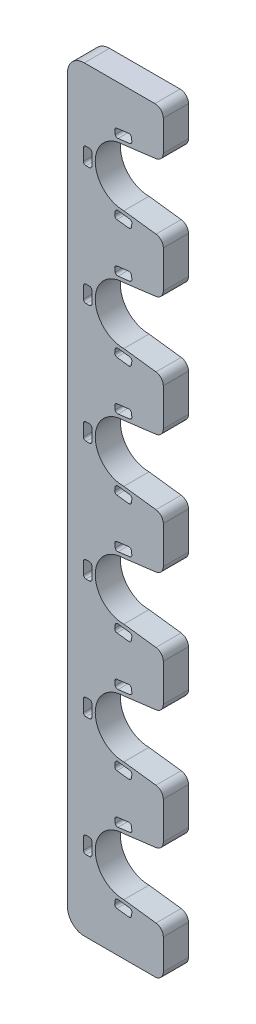
SolidWorks part; units mm, degrees
ref_plane "Front" through (0, 0, 0) normal (0, 0, 1) x (1, 0, 0)
ref_plane "Top" through (0, 0, 0) normal (0, 1, 0) x (1, 0, 0)
ref_plane "Right" through (0, 0, 0) normal (1, 0, 0) x (0, 0, -1)
sketch "Esquisse1" plane through (0, 0, 0) normal (0, 0, 1) x (1, 0, 0)
  line L1 (0, 0) -> (47, 0)
  line L2 (0, 0) -> (0, 450)
  line L3 (0, 450) -> (47, 450)
  line L4 (47, 0) -> (47, 450)
  dimension "D1" = 47
  dimension "D2" = 450
extrude "Boss.-Extru.1" add sketch "Esquisse1" along normal blind 15
sketch "Esquisse2" plane through (0, 0, 15) normal (0, 0, 1) x (1, 0, 0)
  line L0 (23.5, 0) -> (23.5, 450) construction
  line L1 (0, 0) -> (47, 0) construction
  line L2 (47, 450) -> (0, 450) construction
  line L3 (23.5, 225) -> (0, 225) construction
  line L4 (23.5, 154) -> (0, 154) construction
  line L5 (0, 450) -> (0, 0) construction
  line L6 (23.5, 83) -> (0, 83) construction
  line L7 (23.5, 367) -> (0, 367) construction
  line L8 (23.5, 296) -> (0, 296) construction
  circle A0 centre (23.5, 260.5) radius 17
  circle A1 centre (23.5, 189.5) radius 17
  circle A2 centre (23.5, 118.5) radius 17
  circle A3 centre (23.5, 47.5) radius 17
  circle A4 centre (23.5, 402.5) radius 17
  circle A5 centre (23.5, 331.5) radius 17
  dimension "D1" = 71
  dimension "D2" = 34
  dimension "D3" = 71
  dimension "D4" = 71
extrude "Enlèv. mat.-Extru.1" cut sketch "Esquisse2" against normal through all both and the other way through all
sketch "Esquisse3" plane through (0, 0, 15) normal (0, 0, 1) x (1, 0, 0)
  line L0 (23.5, 189.5) -> (23.5, 260.5) construction
  line L1 (23.5, 225) -> (0, 225) construction
  line L2 (0, 450) -> (0, 0) construction
  line L3 (23.5, 243.5) -> (47, 240.5)
  line L4 (47, 0) -> (47, 450) construction
  line L5 (47, 240.5) -> (47, 280.5)
  line L6 (47, 260.5) -> (23.5, 260.5) construction
  line L7 (23.5, 277.5) -> (47, 280.5)
  line L8 (23.5, 243.5) -> (23.5, 277.5)
  line L9 (47, 189.5) -> (23.5, 189.5) construction
  line L10 (23.5, 172.5) -> (47, 169.5)
  line L11 (47, 209.5) -> (47, 169.5)
  line L12 (23.5, 206.5) -> (47, 209.5)
  line L13 (23.5, 206.5) -> (23.5, 172.5)
  line L14 (23.5, 172.5) -> (23.5, 135.5) construction
  line L15 (23.5, 64.5) -> (23.5, 101.5) construction
  line L16 (23.5, 83) -> (0, 83) construction
  line L17 (23.5, 154) -> (0, 154) construction
  line L18 (47, 118.5) -> (23.5, 118.5) construction
  line L19 (23.5, 101.5) -> (23.5, 135.5)
  line L20 (23.5, 101.5) -> (47, 98.5)
  line L21 (47, 98.5) -> (47, 138.5)
  line L22 (23.5, 135.5) -> (47, 138.5)
  line L23 (47, 47.5) -> (23.5, 47.5) construction
  line L24 (23.5, 30.5) -> (47, 27.5)
  line L25 (47, 67.5) -> (47, 27.5)
  line L26 (23.5, 64.5) -> (47, 67.5)
  line L27 (23.5, 64.5) -> (23.5, 30.5)
  line L28 (47, 402.5) -> (23.5, 402.5) construction
  line L29 (47, 331.5) -> (23.5, 331.5) construction
  line L30 (23.5, 296) -> (0, 296) construction
  line L31 (23.5, 367) -> (0, 367) construction
  line L32 (23.5, 385.5) -> (23.5, 348.5) construction
  line L33 (23.5, 385.5) -> (23.5, 419.5)
  line L34 (23.5, 385.5) -> (47, 382.5)
  line L35 (47, 382.5) -> (47, 422.5)
  line L36 (23.5, 419.5) -> (47, 422.5)
  line L37 (23.5, 314.5) -> (47, 311.5)
  line L38 (47, 351.5) -> (47, 311.5)
  line L39 (23.5, 348.5) -> (47, 351.5)
  line L40 (23.5, 348.5) -> (23.5, 314.5)
  circle A0 centre (23.5, 260.5) radius 17 construction
  circle A1 centre (23.5, 118.5) radius 17 construction
  circle A2 centre (23.5, 47.5) radius 17 construction
  dimension "D1" = 3
extrude "Enlèv. mat.-Extru.2" cut sketch "Esquisse3" against normal through all both and the other way through all
sketch "Esquisse4" plane through (0, 0, 15) normal (0, 0, 1) x (1, 0, 0)
  line L0 (47, 450) -> (0, 450) construction
  line L1 (0, 0) -> (-10, 0)
  line L2 (0, 0) -> (0, 450)
  line L3 (0, 450) -> (-10, 450)
  line L4 (-10, 0) -> (-10, 450)
  dimension "D1" = 10
extrude "Boss.-Extru.2" add sketch "Esquisse4" against normal up to vertex (15 mm away) up to point (0, 450, 0)
sketch "Esquisse5" plane through (0, 0, 15) normal (0, 0, 1) x (1, 0, 0)
  line L0 (47, 367) -> (-10, 367) construction
  line L1 (47, 351.5) -> (47, 382.5) construction
  line L2 (-10, 450) -> (-10, 0) construction
  line L3 (47, 296) -> (-10, 296) construction
  line L4 (47, 280.5) -> (47, 311.5) construction
  line L5 (47, 225) -> (-10, 225) construction
  line L6 (47, 209.5) -> (47, 240.5) construction
  line L7 (47, 154) -> (-10, 154) construction
  line L8 (47, 138.5) -> (47, 169.5) construction
  line L9 (47, 83) -> (-10, 83) construction
  line L10 (47, 67.5) -> (47, 98.5) construction
  line L11 (4.5, 189.5) -> (6.5, 189.5) construction
  line L12 (-0.5, 194.5) -> (4.5, 194.5)
  line L13 (-0.5, 194.5) -> (-0.5, 184.5)
  line L14 (-0.5, 184.5) -> (4.5, 184.5)
  line L15 (4.5, 194.5) -> (4.5, 184.5)
  line L16 (47, 169.5) -> (47, 209.5) construction
  line L17 (47, 189.5) -> (6.5, 189.5) construction
  line L18 (18.564, 207.8861) -> (28.4835, 209.1524)
  line L19 (23.5, 206.5) -> (47, 209.5) construction
  line L20 (18.564, 207.8861) -> (17.9308, 212.8458)
  line L21 (17.9308, 212.8458) -> (27.8503, 214.1122)
  line L22 (27.8503, 214.1122) -> (28.4835, 209.1524)
  line L23 (18.564, 207.8861) -> (26.75, 189.5) construction
  line L24 (27.8503, 164.8878) -> (28.4835, 169.8476)
  line L25 (17.9308, 166.1542) -> (27.8503, 164.8878)
  line L26 (18.564, 171.1139) -> (17.9308, 166.1542)
  line L27 (18.564, 171.1139) -> (28.4835, 169.8476)
  line L28 (18.564, 100.1139) -> (26.75, 118.5) construction
  line L29 (47, 118.5) -> (6.5, 118.5) construction
  line L30 (47, 138.5) -> (47, 98.5) construction
  line L31 (4.5, 118.5) -> (6.5, 118.5) construction
  line L32 (18.564, 136.8861) -> (28.4835, 138.1524)
  line L33 (18.564, 136.8861) -> (17.9308, 141.8458)
  line L34 (17.9308, 141.8458) -> (27.8503, 143.1122)
  line L35 (27.8503, 143.1122) -> (28.4835, 138.1524)
  line L36 (27.8503, 93.8878) -> (28.4835, 98.8476)
  line L37 (17.9308, 95.1542) -> (27.8503, 93.8878)
  line L38 (18.564, 100.1139) -> (17.9308, 95.1542)
  line L39 (18.564, 100.1139) -> (28.4835, 98.8476)
  line L40 (4.5, 113.5) -> (4.5, 123.5)
  line L41 (-0.5, 123.5) -> (4.5, 123.5)
  line L42 (-0.5, 113.5) -> (-0.5, 123.5)
  line L43 (-0.5, 113.5) -> (4.5, 113.5)
  line L44 (4.5, 47.5) -> (6.5, 47.5) construction
  line L45 (47, 27.5) -> (47, 67.5) construction
  line L46 (47, 47.5) -> (6.5, 47.5) construction
  line L47 (18.564, 65.8861) -> (26.75, 47.5) construction
  line L48 (-0.5, 52.5) -> (4.5, 52.5)
  line L49 (-0.5, 52.5) -> (-0.5, 42.5)
  line L50 (-0.5, 42.5) -> (4.5, 42.5)
  line L51 (4.5, 52.5) -> (4.5, 42.5)
  line L52 (18.564, 65.8861) -> (28.4835, 67.1524)
  line L53 (18.564, 65.8861) -> (17.9308, 70.8458)
  line L54 (17.9308, 70.8458) -> (27.8503, 72.1122)
  line L55 (27.8503, 72.1122) -> (28.4835, 67.1524)
  line L56 (27.8503, 22.8878) -> (28.4835, 27.8476)
  line L57 (17.9308, 24.1542) -> (27.8503, 22.8878)
  line L58 (18.564, 29.1139) -> (17.9308, 24.1542)
  line L59 (18.564, 29.1139) -> (28.4835, 27.8476)
  line L60 (18.564, 384.1139) -> (26.75, 402.5) construction
  line L61 (47, 402.5) -> (6.5, 402.5) construction
  line L62 (47, 422.5) -> (47, 382.5) construction
  line L63 (4.5, 402.5) -> (6.5, 402.5) construction
  line L64 (4.5, 331.5) -> (6.5, 331.5) construction
  line L65 (47, 311.5) -> (47, 351.5) construction
  line L66 (47, 331.5) -> (6.5, 331.5) construction
  line L67 (18.564, 349.8861) -> (26.75, 331.5) construction
  line L68 (18.564, 242.1139) -> (26.75, 260.5) construction
  line L69 (47, 260.5) -> (6.5, 260.5) construction
  line L70 (47, 280.5) -> (47, 240.5) construction
  line L71 (4.5, 260.5) -> (6.5, 260.5) construction
  line L72 (47, 367) -> (-10, 367) construction
  line L73 (47, 296) -> (-10, 296) construction
  line L74 (18.564, 420.8861) -> (28.4835, 422.1524)
  line L75 (18.564, 420.8861) -> (17.9308, 425.8458)
  line L76 (17.9308, 425.8458) -> (27.8503, 427.1122)
  line L77 (27.8503, 427.1122) -> (28.4835, 422.1524)
  line L78 (27.8503, 377.8878) -> (28.4835, 382.8476)
  line L79 (17.9308, 379.1542) -> (27.8503, 377.8878)
  line L80 (18.564, 384.1139) -> (17.9308, 379.1542)
  line L81 (18.564, 384.1139) -> (28.4835, 382.8476)
  line L82 (4.5, 397.5) -> (4.5, 407.5)
  line L83 (-0.5, 407.5) -> (4.5, 407.5)
  line L84 (-0.5, 397.5) -> (-0.5, 407.5)
  line L85 (-0.5, 397.5) -> (4.5, 397.5)
  line L86 (-0.5, 336.5) -> (4.5, 336.5)
  line L87 (-0.5, 336.5) -> (-0.5, 326.5)
  line L88 (-0.5, 326.5) -> (4.5, 326.5)
  line L89 (4.5, 336.5) -> (4.5, 326.5)
  line L90 (18.564, 349.8861) -> (28.4835, 351.1524)
  line L91 (18.564, 349.8861) -> (17.9308, 354.8458)
  line L92 (17.9308, 354.8458) -> (27.8503, 356.1122)
  line L93 (27.8503, 356.1122) -> (28.4835, 351.1524)
  line L94 (27.8503, 306.8878) -> (28.4835, 311.8476)
  line L95 (17.9308, 308.1542) -> (27.8503, 306.8878)
  line L96 (18.564, 313.1139) -> (17.9308, 308.1542)
  line L97 (18.564, 313.1139) -> (28.4835, 311.8476)
  line L98 (18.564, 278.8861) -> (28.4835, 280.1524)
  line L99 (18.564, 278.8861) -> (17.9308, 283.8458)
  line L100 (17.9308, 283.8458) -> (27.8503, 285.1122)
  line L101 (27.8503, 285.1122) -> (28.4835, 280.1524)
  line L102 (27.8503, 235.8878) -> (28.4835, 240.8476)
  line L103 (17.9308, 237.1542) -> (27.8503, 235.8878)
  line L104 (18.564, 242.1139) -> (17.9308, 237.1542)
  line L105 (18.564, 242.1139) -> (28.4835, 240.8476)
  line L106 (4.5, 255.5) -> (4.5, 265.5)
  line L107 (-0.5, 265.5) -> (4.5, 265.5)
  line L108 (-0.5, 255.5) -> (-0.5, 265.5)
  line L109 (-0.5, 255.5) -> (4.5, 255.5)
  arc A1 (23.5, 206.5) -> (23.5, 172.5) centre (23.5, 189.5) ccw construction
  dimension "D1" = 5
  dimension "D2" = 10
  dimension "D3" = 2
  dimension "D4" = 10
  dimension "D5" = 5
  dimension "D6" = 2
  dimension "D7" = 66
extrude "Enlèv. mat.-Extru.3" cut sketch "Esquisse5" against normal blind 10
fillet "Congé1" radius 5 14 edges at (47, 422.5, 7.5) (47, 382.5, 7.5) (47, 351.5, 7.5) (47, 311.5, 7.5) (47, 280.5, 7.5) (47, 240.5, 7.5) (47, 209.5, 7.5) (47, 169.5, 7.5) (47, 138.5, 7.5) (47, 98.5, 7.5) (47, 67.5, 7.5) (47, 27.5, 7.5) (47, 450, 7.5) (47, 0, 7.5)
fillet "Congé2" radius 10 2 edges at (-10, 450, 7.5) (-10, 0, 7.5)
fillet "Congé3" radius 1.5 72 edges at (17.9308, 425.8458, 10) (18.564, 420.8861, 10) (28.4835, 422.1524, 10) (27.8503, 427.1122, 10) (28.4835, 311.8476, 10) (27.8503, 306.8878, 10) (17.9308, 308.1542, 10) (18.564, 313.1139, 10) (-0.5, 336.5, 10) (4.5, 336.5, 10) (-0.5, 326.5, 10) (4.5, 326.5, 10) (28.4835, 351.1524, 10) (18.564, 349.8861, 10) (17.9308, 354.8458, 10) (27.8503, 356.1122, 10) (28.4835, 382.8476, 10) (27.8503, 377.8878, 10) (17.9308, 379.1542, 10) (18.564, 384.1139, 10) (4.5, 397.5, 10) (-0.5, 397.5, 10) (-0.5, 407.5, 10) (4.5, 407.5, 10) (27.8503, 22.8878, 10) (17.9308, 24.1542, 10) (18.564, 29.1139, 10) (28.4835, 27.8476, 10) (4.5, 42.5, 10) (-0.5, 42.5, 10) (-0.5, 52.5, 10) (4.5, 52.5, 10) (18.564, 65.8861, 10) (17.9308, 70.8458, 10) (27.8503, 72.1122, 10) (28.4835, 67.1524, 10) (27.8503, 93.8878, 10) (17.9308, 95.1542, 10) (28.4835, 98.8476, 10) (18.564, 100.1139, 10) (4.5, 113.5, 10) (-0.5, 113.5, 10) (-0.5, 123.5, 10) (4.5, 123.5, 10) (28.4835, 138.1524, 10) (27.8503, 143.1122, 10) (17.9308, 141.8458, 10) (18.564, 136.8861, 10) (17.9308, 166.1542, 10) (27.8503, 164.8878, 10) (28.4835, 169.8476, 10) (18.564, 171.1139, 10) (-0.5, 184.5, 10) (4.5, 184.5, 10) (4.5, 194.5, 10) (-0.5, 194.5, 10) (17.9308, 212.8458, 10) (18.564, 207.8861, 10) (28.4835, 209.1524, 10) (27.8503, 214.1122, 10) (28.4835, 240.8476, 10) (27.8503, 235.8878, 10) (17.9308, 237.1542, 10) (18.564, 242.1139, 10) (4.5, 255.5, 10) (4.5, 265.5, 10) (-0.5, 265.5, 10) (-0.5, 255.5, 10) (27.8503, 285.1122, 10) (28.4835, 280.1524, 10) (18.564, 278.8861, 10) (17.9308, 283.8458, 10)
